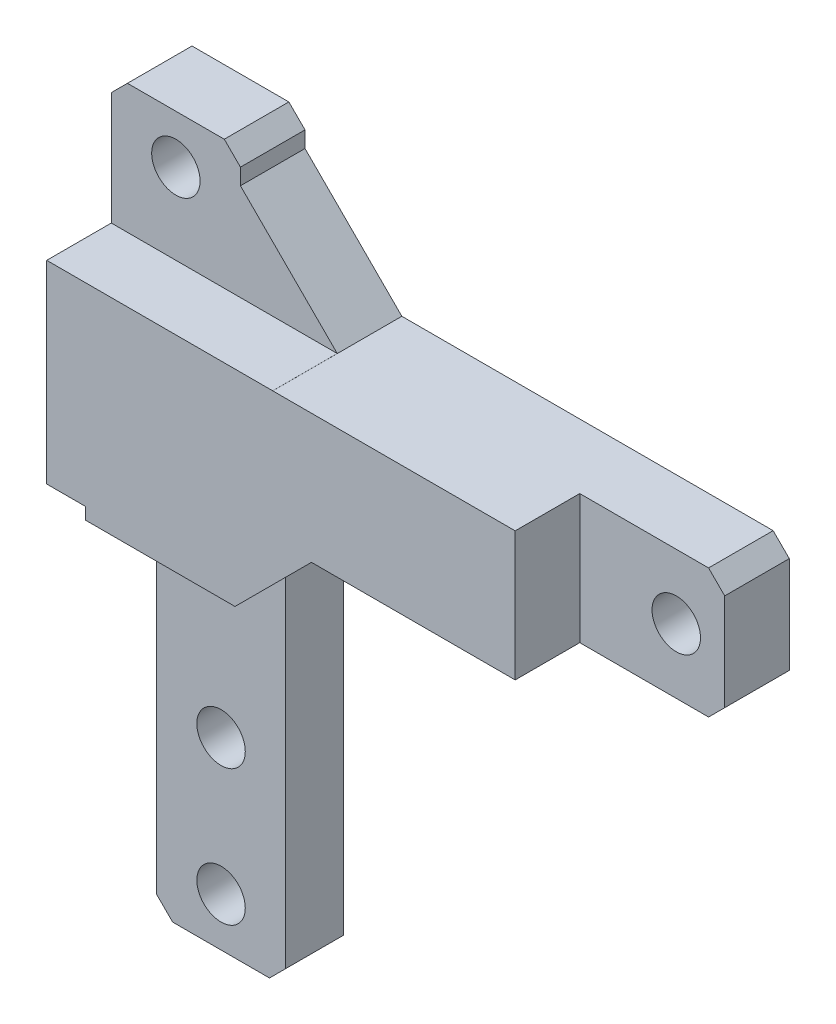
SolidWorks part; units mm, degrees
ref_plane "前视基准面" through (0, 0, 0) normal (0, 0, 1) x (1, 0, 0)
ref_plane "上视基准面" through (0, 0, 0) normal (0, 1, 0) x (1, 0, 0)
ref_plane "右视基准面" through (0, 0, 0) normal (1, 0, 0) x (0, 0, -1)
other "Configuration Table"
sketch "草图1" plane through (0, 0, 0) normal (0, 0, 1) x (1, 0, 0)
  line L0 (-4.3, -2.5) -> (9.5, -2.5)
  line L1 (-5.5, 1.5) -> (9.5, 1.5)
  line L4 (9.5, 1.5) -> (9.5, -2.5)
  line L8 (-9.5, 1.5) -> (-9.5, 5.5)
  line L9 (-9.5, 5.5) -> (-5.5, 5.5)
  line L11 (-5.5, 1.5) -> (-5.5, 5.5)
  line L12 (-9.5, 1.5) -> (-9.5, -4.5)
  line L13 (-8.3, -4.5) -> (-8.3, -16.5)
  line L14 (-8.3, -16.5) -> (-4.3, -16.5)
  line L15 (-4.3, -16.5) -> (-4.3, -2.5)
  line L16 (-9.5, -4.5) -> (-8.3, -4.5)
  circle A0 centre (8, -0.5) radius 0.75
  circle A1 centre (-7.5, 4) radius 0.75
  circle A2 centre (-6.3, -15) radius 0.75
  circle A3 centre (-6.3, -10.8) radius 0.75
  point P0 (0, 0)
  dimension "D16" = 1.5
  dimension "D2" = 6
  dimension "D4" = 2
  dimension "D5" = 1.5
  dimension "D6" = 10
  dimension "D7" = 4
  dimension "D9" = 2
  dimension "D10" = 1.5
  dimension "D11" = 4
  dimension "D12" = 4
  dimension "D13" = 2
  dimension "D14" = 19
  dimension "D17" = 4.2
  dimension "D18" = 1.5
  dimension "D19" = 2
extrude "凸台-拉伸1" add sketch "草图1" along normal blind 4
sketch "草图2" plane through (0, 0, 4) normal (0, 0, 1) x (1, 0, 0)
  line L0 (-8.3, -4.8687) -> (-4.3, -4.8687)
  line L10 (9.5, -2.5) -> (9.5, 1.5)
  line L11 (9.5, 1.5) -> (-5.5, 1.5)
  line L12 (-5.5, 1.5) -> (-5.5, 5.5)
  line L13 (-5.5, 5.5) -> (-9.5, 5.5)
  line L14 (-9.5, 5.5) -> (-9.5, -4.5)
  line L15 (-9.5, -4.5) -> (-8.3, -4.5)
  line L16 (-8.3, -4.5) -> (-8.3, -16.5)
  line L17 (-8.3, -16.5) -> (-4.3, -16.5)
  line L18 (-4.3, -16.5) -> (-4.3, -2.5)
  line L19 (-4.3, -2.5) -> (9.5, -2.5)
  line L26 (-8.3, -4.8687) -> (-8.3, -16.5)
  line L27 (-8.3, -16.5) -> (-4.3, -16.5)
  line L28 (-4.3, -16.5) -> (-4.3, -4.8687)
  circle A0 centre (-6.3, -15) radius 0.75 construction
  circle A1 centre (-6.3, -10.8) radius 0.75 construction
  circle A2 centre (-6.3, -15) radius 0.75
  circle A3 centre (-6.3, -10.8) radius 0.75
  dimension "D1" = 0
extrude "切除-拉伸1" cut sketch "草图2" against normal blind 2.2
sketch "草图3" plane through (0, 0, 4) normal (0, 0, -1) x (-1, 0, 0)
  line L0 (-5.0101, 1.5) -> (-5.0101, -2.5)
  line L1 (5.5, 1.5011) -> (9.5, 1.5011)
  line L10 (-9.5, 1.5) -> (-9.5, -2.5)
  line L11 (-9.5, -2.5) -> (4.3, -2.5)
  line L12 (4.3, -2.5) -> (4.3, -16.5)
  line L13 (4.3, -16.5) -> (8.3, -16.5)
  line L14 (8.3, -16.5) -> (8.3, -4.5)
  line L15 (8.3, -4.5) -> (9.5, -4.5)
  line L16 (9.5, -4.5) -> (9.5, 5.5)
  line L17 (9.5, 5.5) -> (5.5, 5.5)
  line L18 (5.5, 5.5) -> (5.5, 1.5)
  line L19 (5.5, 1.5) -> (-9.5, 1.5)
  line L20 (-9.5, 1.5) -> (-9.5, -2.5)
  line L21 (-9.5, -2.5) -> (-5.0101, -2.5)
  line L26 (9.5, 1.5011) -> (9.5, 5.5)
  line L27 (9.5, 5.5) -> (5.5, 5.5)
  line L28 (5.5, 5.5) -> (5.5, 1.5011)
  line L29 (-5.0101, 1.5) -> (-9.5, 1.5)
  circle A0 centre (-8, -0.5) radius 0.75 construction
  circle A1 centre (7.5, 4) radius 0.75 construction
  circle A2 centre (-8, -0.5) radius 0.75
  circle A3 centre (7.5, 4) radius 0.75
  dimension "D1" = 0
extrude "切除-拉伸2" cut sketch "草图3" along normal blind 2
chamfer "倒角1" distance 3 angle 45 2 edges at (-4.3, -2.5, 2) (-5.5, 1.5, 2)
chamfer "倒角2" distance 0.5 angle 45 6 edges at (-4.3, -16.5, 0.9) (-8.3, -16.5, 0.9) (-9.5, 5.5, 1) (9.5, -2.5, 1) (9.5, 1.5, 1) (-5.5, 5.5, 1)
